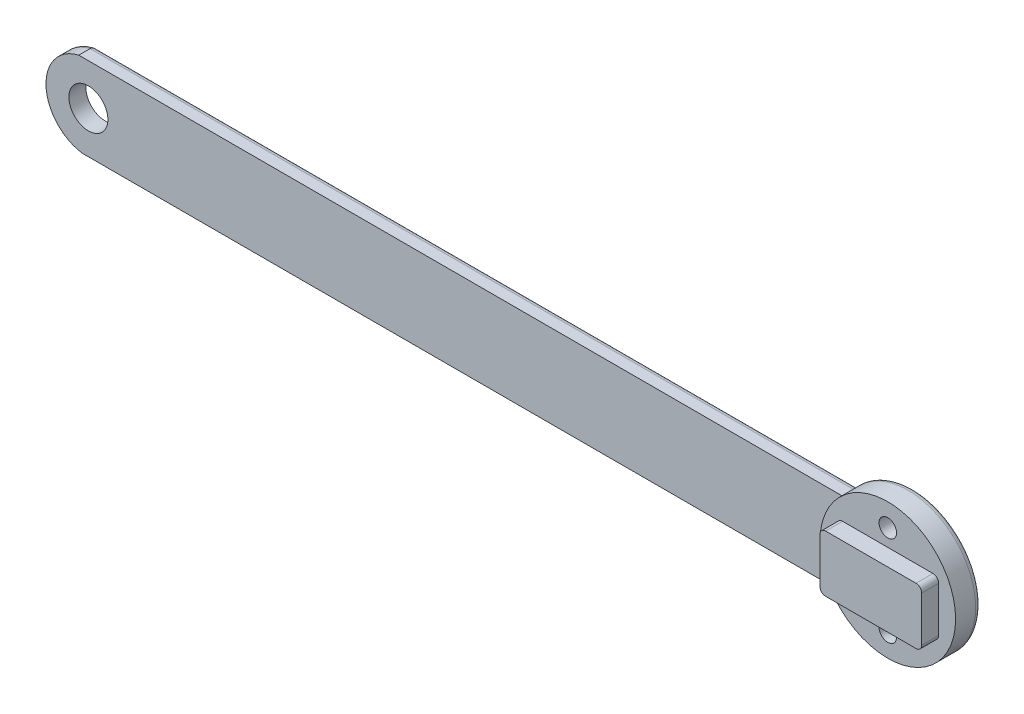
SolidWorks part; units mm, degrees
ref_plane "Plan de face" through (0, 0, 0) normal (0, 0, 1) x (1, 0, 0)
ref_plane "Plan de dessus" through (0, 0, 0) normal (0, 1, 0) x (1, 0, 0)
ref_plane "Plan de droite" through (0, 0, 0) normal (1, 0, 0) x (0, 0, -1)
sketch "Esquisse1" plane through (0, 0, 0) normal (0, 0, 1) x (1, 0, 0)
  line L2 (-1.6982, 7.3052) -> (133.4798, 7.3052)
  line L3 (-1.1002, -7.4189) -> (133.5681, -7.4189)
  circle A0 centre (0, 0) radius 3.45
  arc A1 (133.5681, -7.4189) -> (133.4798, 7.3052) centre (143, 0) ccw
  arc A3 (-1.6982, 7.3052) -> (-1.1002, -7.4189) centre (0, 0) ccw
  point P4 (0, 0)
  point P10 (132.262, 7.3052)
  point P11 (133.4798, 7.4998)
  point P12 (133.4798, -7.4883)
  point P13 (133.4798, -7.4189)
  dimension "D1" = 6.9
  dimension "D2" = 24
  dimension "D4" = 15
  dimension "D3" = 143
extrude "Boss.-Extru.1" add sketch "Esquisse1" along normal blind 3
sketch "Esquisse2" plane through (0, 0, 3) normal (0, 0, 1) x (1, 0, 0)
  circle A0 centre (143, 0) radius 12
extrude "Boss.-Extru.2" add sketch "Esquisse2" along normal blind 1.55
sketch "Esquisse3" plane through (0, 0, 4.55) normal (0, 0, 1) x (1, 0, 0)
  line L1 (135, -5) -> (151, -5)
  line L2 (134, -4) -> (134, 4)
  line L3 (135, 5) -> (151, 5)
  line L4 (152, -4) -> (152, 4)
  line L5 (134, -5) -> (152, 5) construction
  line L6 (134, 5) -> (152, -5) construction
  arc A0 (151, 5) -> (152, 4) centre (151, 4) cw
  arc A1 (152, -4) -> (151, -5) centre (151, -4) cw
  arc A2 (135, -5) -> (134, -4) centre (135, -4) cw
  arc A3 (134, 4) -> (135, 5) centre (135, 4) cw
  point P0 (143, 0)
  dimension "D3" = 1
  dimension "D1" = 18
  dimension "D2" = 10
extrude "Boss.-Extru.3" add sketch "Esquisse3" along normal blind 3
sketch "Esquisse4" plane through (0, 0, 4.55) normal (0, 0, 1) x (1, 0, 0)
  line L0 (151, 5) -> (135, 5) construction
  line L1 (152, -4) -> (152, 4) construction
  line L2 (152, -4) -> (152, 4) construction
  line L3 (152, 0) -> (147.3986, 0) construction
  circle A0 centre (143, 8) radius 1.55
  circle A2 centre (143, -8) radius 1.55
  dimension "D2" = 3.1
  dimension "D1" = 3
  dimension "D3" = 9
fillet "Congé1" radius 1 4 edges at (-7.4938, -0.3043, 0) (154.9998, 0.072, 0) (66.2339, -7.4189, 0) (65.8908, 7.3052, 0)
extrude "Enlèv. mat.-Extru.1" cut sketch "Esquisse4" against normal through all
fillet "Congé2" radius 0.25 2 edges at (141.45, -8, 0) (144.55, 8, 0)
